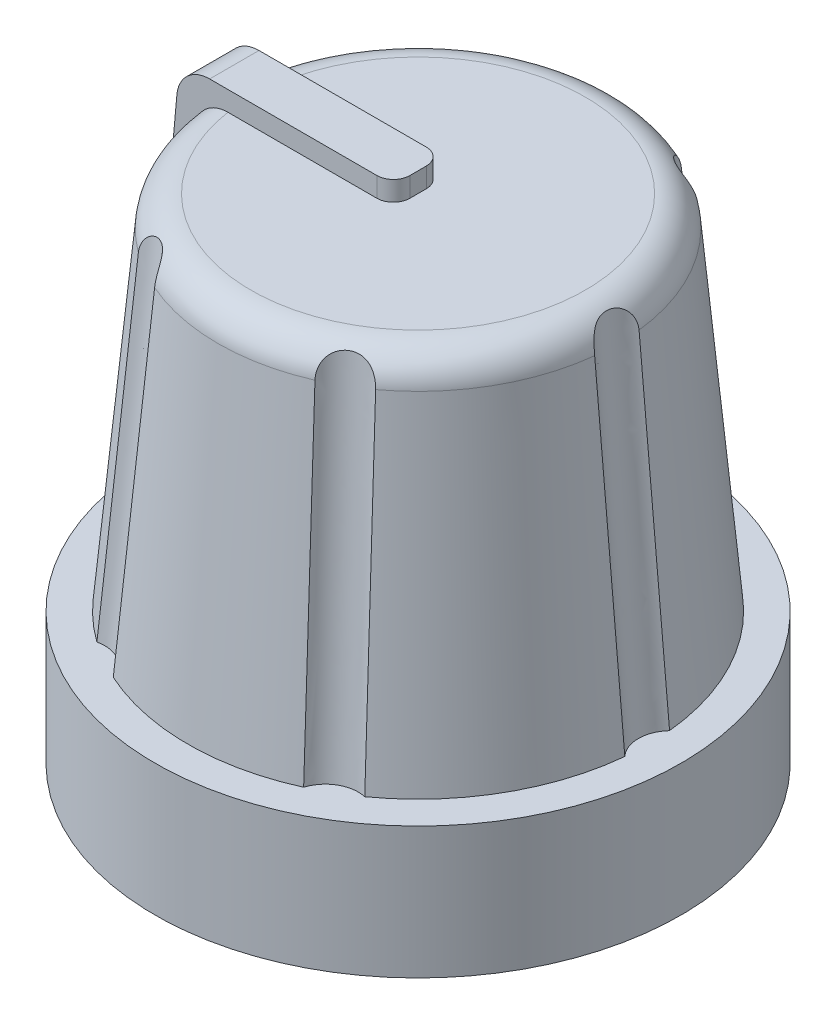
SolidWorks part; units mm, degrees
ref_plane "Plan de face" through (0, 0, 0) normal (0, 0, 1) x (1, 0, 0)
ref_plane "Plan de dessus" through (0, 0, 0) normal (0, 1, 0) x (1, 0, 0)
ref_plane "Plan de droite" through (0, 0, 0) normal (1, 0, 0) x (0, 0, -1)
sketch "Esquisse1" plane through (0, 0, 0) normal (0, 0, 1) x (1, 0, 0)
  line L0 (0, 13.5) -> (0, 15)
  line L1 (0, 15) -> (6, 15)
  line L2 (6, 15) -> (7, 4)
  line L3 (7, 4) -> (8, 4)
  line L4 (8, 4) -> (8, 0)
  line L5 (8, 0) -> (3, 0)
  line L6 (3, 0) -> (3, 13.5)
  line L7 (3, 13.5) -> (0, 13.5)
  dimension "D1" = 3
  dimension "D2" = 13.5
  dimension "D3" = 15
  dimension "D4" = 4
  dimension "D5" = 8
  dimension "D6" = 6
  dimension "D7" = 1
revolve "Révolution1" add sketch "Esquisse1" angle 360 about L0
sketch "Esquisse2" plane through (0, 0, 0) normal (0, 0, 1) x (1, 0, 0)
  line L0 (0, 13.844) -> (0, 15.6)
  line L1 (0, 15.6) -> (-6.5, 15.6)
  line L2 (-6.5, 15.6) -> (-7.9177, 0.0051)
  line L3 (-7.9177, 0.0051) -> (-6.239, 0)
  line L5 (-6.239, 0) -> (-4.9742, 13.844)
  line L6 (-4.9742, 13.844) -> (0, 13.844)
  line L7 (6, 15) -> (-6, 15) construction
  line L8 (-8, 0) -> (8, 0) construction
  line L9 (-6, 15) -> (-7, 4) construction
  dimension "D1" = 6.5
  dimension "D2" = 0.6
extrude "Boss.-Extru.1" add sketch "Esquisse2" along normal mid plane 1.5
sketch "Esquisse4" plane through (0, 0, 0) normal (0, 0, 1) x (1, 0, 0)
  line L0 (6, 15) -> (7, 4)
sketch "Esquisse5" plane through (0, 15, 0) normal (0, 1, 0) x (1, 0, 0)
  line L0 (6, 0) -> (7, 0) construction
  circle A0 centre (6.7, 0) radius 1
  arc A1 (-5.9529, -0.75) -> (-5.9529, 0.75) centre (0, 0) ccw construction
  point P5 (6, 0)
  dimension "D1" = 2
  dimension "D2" = 0.7
sweep "Enlèvement de matière-Balayage1" cut profiles "Esquisse5" path "Esquisse4"
ref_axis "Axe1" through (0, 4, 0) along (0, -1, 0)
pattern_circular "Répétition circulaire1" count 6 over 360 about axis through (0, 4, 0) along (0, -1, 0) skipping 3 of "Enlèvement de matière-Balayage1"
fillet "Congé1" radius 1 1 edges at (-5.1771, 15, 3.0328)
fillet "Congé3" radius 1 1 edges at (-6.5, 15.6, 0)
fillet "Congé2" radius 0.5 2 edges at (0, 15.3, -0.75) (0, 15.3, 0.75)
